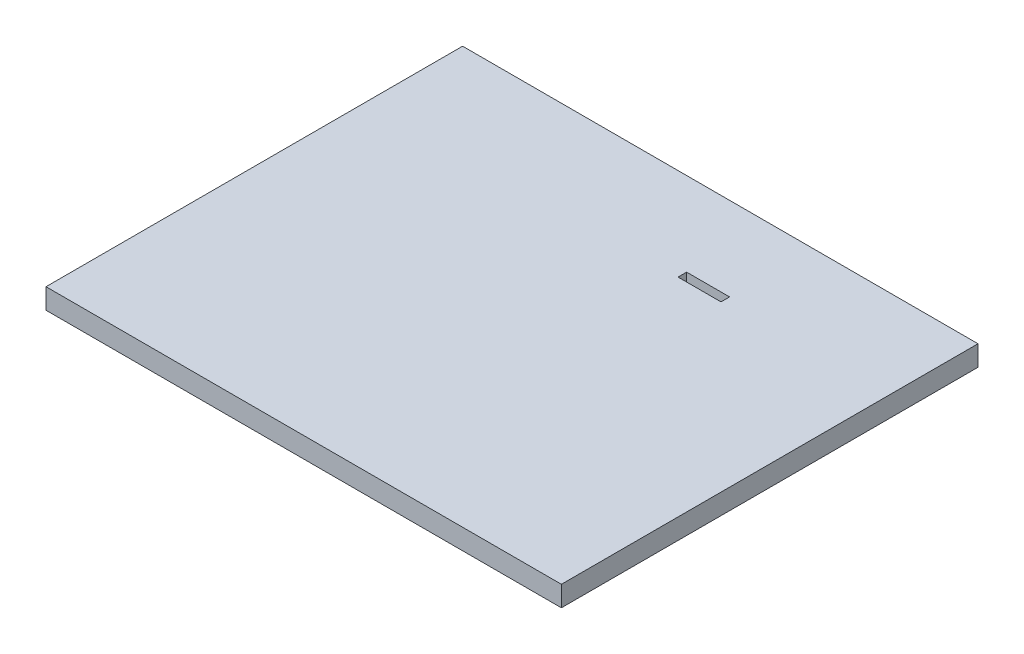
SolidWorks part; units mm, degrees
ref_plane "前视基准面" through (0, 0, 0) normal (0, 0, 1) x (1, 0, 0)
ref_plane "上视基准面" through (0, 0, 0) normal (0, 1, 0) x (1, 0, 0)
ref_plane "右视基准面" through (0, 0, 0) normal (1, 0, 0) x (0, 0, -1)
sketch "草图1" plane through (0, 0, 0) normal (0, 1, 0) x (1, 0, 0)
  line L1 (0, 0) -> (240, 0)
  line L2 (0, 0) -> (0, -194)
  line L3 (0, -194) -> (240, -194)
  line L4 (240, 0) -> (240, -194)
  dimension "D1" = 194
  dimension "D2" = 240
extrude "凸台-拉伸1" add sketch "草图1" along normal blind 9.5
sketch "草图2" plane through (0, 9.5, 0) normal (0, 1, 0) x (1, 0, 0)
  line L0 (0, -97) -> (240, -97) construction
  line L1 (0, 0) -> (0, -194) construction
  line L2 (240, -194) -> (240, 0) construction
ref_plane "基准面1" through (0, 0, 97) normal (0, 0, 1) x (1, 0, 0)
sketch "草图3" plane through (0, 9.5, 0) normal (0, 1, 0) x (1, 0, 0)
  line L1 (143.2815, -38.9591) -> (163.2815, -38.9591)
  line L2 (143.2815, -38.9591) -> (143.2815, -42.9591)
  line L3 (143.2815, -42.9591) -> (163.2815, -42.9591)
  line L4 (163.2815, -38.9591) -> (163.2815, -42.9591)
  dimension "D1" = 20
  dimension "D2" = 4
extrude "切除-拉伸1" cut sketch "草图3" against normal through all
